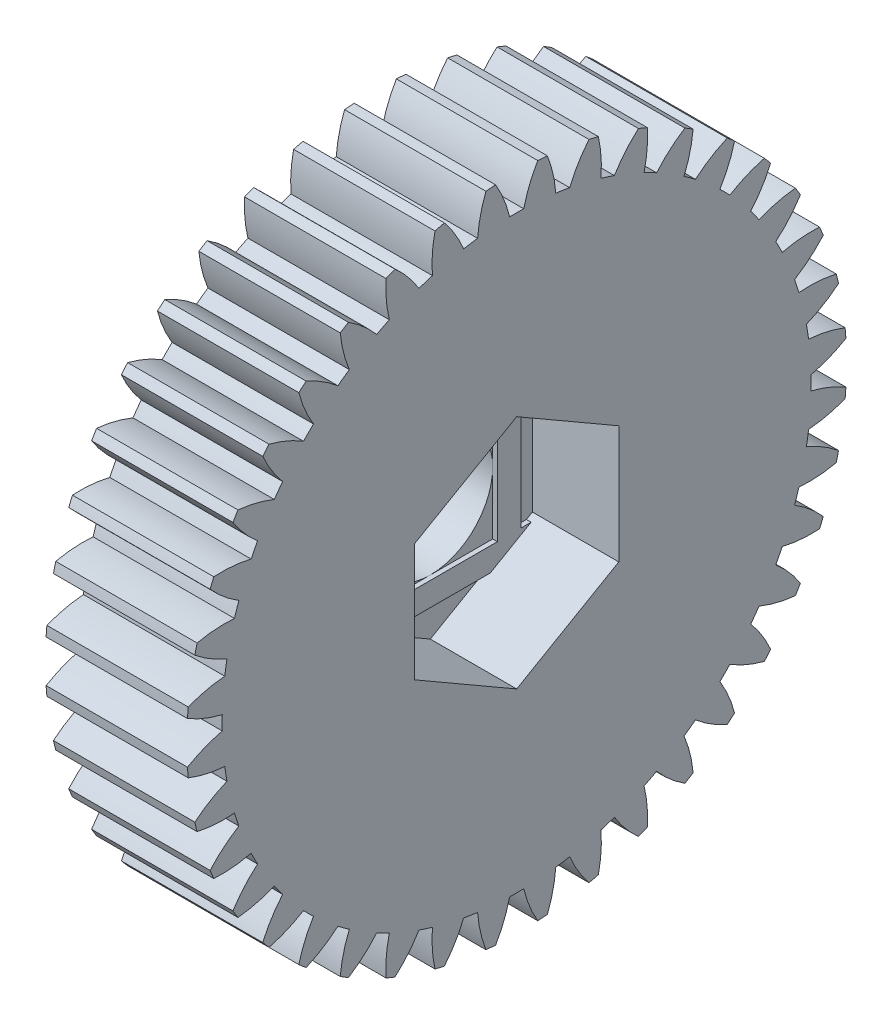
SolidWorks part; units mm, degrees
ref_plane "Plane1" through (0, 0, 0) normal (0, 0, 1) x (1, 0, 0)
ref_plane "Plane2" through (0, 0, 0) normal (0, 1, 0) x (1, 0, 0)
ref_plane "Plane3" through (0, 0, 0) normal (1, 0, 0) x (0, 0, -1)
sketch "HoldingSke" plane through (0, 0, 0) normal (0, 1, 0) x (1, 0, 0)
  line L0 (0, 0) -> (0.766, -0.6428)
  line L1 (-15, 0) -> (100, 0) construction
  line L2 (0, 0) -> (-2.1039, 2.3779)
  line L3 (0, 0) -> (-11.863, 4.5341)
  line L4 (0, 0) -> (6.6156, 5.5511)
  line L5 (0, 0) -> (-46.8476, -17.4728)
  line L6 (0, 0) -> (-7.4607, -5.0337)
  line L7 (-2.1039, 2.3779) -> (8.6586, 51.2059)
  line L8 (-76.2, 54.61) -> (-75.5, 54.61)
  line L9 (-71.009, 38.7566) -> (-53.1078, 45.2721)
  line L10 (-76.2, 71.12) -> (104.1128, 71.12)
  line L11 (0, 0) -> (-9, 0)
  line L12 (-76.2, 101.6) -> (-76.162, 101.6)
  line L13 (24.9733, 27.94) -> (52.9518, 28.4284)
  line L14 (24.9733, 27.94) -> (24.9743, 27.94)
  line L15 (24.9733, 27.94) -> (100.4006, 29.5858)
  line L16 (-63.627, -1) -> (-12.827, -1)
  circle A0 centre (0, 0) radius 2
  circle A1 centre (0, 0) radius 18.749
  circle A2 centre (0, 0) radius 37.5
  circle A3 centre (0, 0) radius 2
  dimension "MHD" = 37.498
  dimension "Hub_dia" = 75
  dimension "Bore" = 4
  dimension "MBD" = 4
  dimension "Num_teeth" = 40
  dimension "Pitch" = 1
  dimension "Overall_len" = 50
  dimension "Show_teeth" = 40
  dimension "Thickness" = 9
  dimension "OAL" = 50.0001
  dimension "T_dim" = 0.7
  dimension "Ap" = 20
  dimension "H" = 19.05
  dimension "Pitch_radius" = 180.3128
  dimension "Width" = 9
  dimension "Backlash" = 0.038
  dimension "Addendum_fac" = 1
  dimension "Dedendum_fac" = 1.25
  dimension "Clearance_fac" = 0.25
  dimension "Dedendum_add" = 0.001
  dimension "Module" = 1
sketch "BasProSke" plane through (0, 0, 0) normal (0, 1, 0) x (1, 0, 0)
  line L0 (-10, 0) -> (60, 0) construction
  line L1 (0, 0) -> (0, 21)
  line L2 (0, 0) -> (9, 0)
  line L3 (9, 0) -> (9, 21)
  line L4 (9, 21) -> (0, 21)
  dimension "Thickness" = 9
  dimension "Diameter" = 42
revolve "Base-Revolve" add sketch "BasProSke" angle 360 about L0
sketch "TooCutSke" plane through (0, 0, 0) normal (1, 0, 0) x (0, 0, -1)
  line L1 (0, 0) -> (0, 107) construction
  line L2 (0, 0) -> (-0.8517, 19.9819) construction
  line L3 (0, 0) -> (-3.1363, 39.8509) construction
  line L4 (-0.8517, 19.9819) -> (-1.5682, 19.9255) construction
  arc A0 (0.4487, 18.7436) -> (-0.4487, 18.7436) centre (0, 0) ccw
  arc A1 (1.3547, 20.9817) -> (-1.3547, 20.9817) centre (0, 0) ccw
  circle A2 centre (0, 0) radius 20 construction
  circle A3 centre (0, 0) radius 18.7939 construction
  arc A4 (-0.4487, 18.7436) -> (-1.3547, 20.9817) centre (-8.2322, 16.895) ccw
  arc A5 (1.3547, 20.9817) -> (0.4487, 18.7436) centre (8.2322, 16.895) ccw
  dimension "Root_dia" = 37.498
  dimension "Overcut_dia" = 42.0508
  dimension "Pitch_dia" = 40
  dimension "Base_dia" = 37.5877
  dimension "Flank_rad" = 8
  dimension "Half_ang" = 4.5
  dimension "Half_CT" = 0.7187
extrude "ToothCut" cut sketch "TooCutSke" along normal through all
fillet "Breaks" [suppressed] radius 0.02 tangent propagation no
fillet "RootFillets" [suppressed] radius 0.251
pattern_circular "TeethCuts" count 40 every 9 about axis through (-10, 0, 0) along (1, 0, 0) of "ToothCut", "RootFillets", "Breaks"
sketch "HubNeaOneSke" plane through (0, 0, 0) normal (-1, 0, 0) x (0, 0, 1)
  circle A0 centre (0, 0) radius 18.749
  dimension "Diameter" = 37.498
extrude "HubNearOne" [suppressed] add sketch "HubNeaOneSke" along normal blind 41.0001
sketch "HubNeaBotSke" plane through (0, 0, 0) normal (-1, 0, 0) x (0, 0, 1)
  circle A0 centre (0, 0) radius 18.749
  dimension "Diameter" = 37.498
extrude "HubNearBoth" [suppressed] add sketch "HubNeaBotSke" along normal blind 20.5
ref_plane "FarPln" through (9, 0, 0) normal (1, 0, 0) x (0, 0, -1)
sketch "HubFarSke" plane through (9, 0, 0) normal (1, 0, 0) x (0, 0, -1)
  circle A0 centre (0, 0) radius 18.749
  dimension "Diameter" = 37.498
extrude "HubFar" [suppressed] add sketch "HubFarSke" along normal blind 20.5
sketch "BorSke" plane through (0, 0, 0) normal (1, 0, 0) x (0, 0, -1)
  circle A0 centre (0, 0) radius 2
  dimension "Diameter" = 4
extrude "Bore" cut sketch "BorSke" along normal mid plane 100.0001
sketch "KeySke" plane through (0, 0, 0) normal (1, 0, 0) x (0, 0, -1)
  line L0 (-0.8, 0) -> (-0.8, 2.7)
  line L1 (-0.8, 2.7) -> (0.8, 2.7)
  line L2 (0.8, 2.7) -> (0.8, 0)
  line L3 (0, 0) -> (0, 34) construction
  line L4 (-0.8, 0) -> (0.8, 0)
  dimension "Offset" = 2.7
  dimension "Width" = 1.6
extrude "Keyway" [suppressed] cut sketch "KeySke" along normal mid plane 100.0001
pattern_circular "Keyway2" [suppressed] count 2 every 90 about axis through (-10, 0, 0) along (1, 0, 0) reverse direction yes
sketch "Sketch1" plane through (9, 0, 0) normal (1, 0, 0) x (0, 0, -1)
  line L1 (0, 7.5056) -> (-6.5, 3.7528)
  line L2 (-6.5, 3.7528) -> (-6.5, -3.7528)
  line L3 (-6.5, -3.7528) -> (0, -7.5056)
  line L4 (0, -7.5056) -> (6.5, -3.7528)
  line L5 (6.5, -3.7528) -> (6.5, 3.7528)
  line L6 (6.5, 3.7528) -> (0, 7.5056)
  circle A0 centre (0, 0) radius 7.5056
  circle A2 centre (0, 0) radius 6.5 construction
  circle A3 centre (0, 0) radius 3.9725
  dimension "D1" = 7.945
  dimension "D2" = 13
extrude "Cut-Extrude1" cut sketch "Sketch1" against normal blind 5.5 contours L1 L2 L3 L4 L5 L6
extrude "Cut-Extrude2" cut sketch "Sketch1<7>" against normal through all contours A3 region at (9, 0, 0)
sketch "Sketch1<7>" plane through (9, 0, 0) normal (1, 0, 0) x (0, 0, -1) same geometry as "Sketch1"
sketch "Sketch2" plane through (0, 0, 0) normal (-1, 0, 0) x (0, 0, 1)
  circle A0 centre (0, 0) radius 6
  circle A1 centre (0, 0) radius 4
  dimension "D1" = 12
  dimension "D2" = 8
extrude "Boss-Extrude1" add sketch "Sketch2" along normal blind 1.3
sketch "Sketch3" plane through (3.5, 0, 0) normal (1, 0, 0) x (0, 0, -1)
  line L1 (3.9725, 3.9725) -> (-3.9725, 3.9725)
  line L2 (3.9725, 3.9725) -> (3.9725, -3.9725)
  line L3 (3.9725, -3.9725) -> (-3.9725, -3.9725)
  line L4 (-3.9725, 3.9725) -> (-3.9725, -3.9725)
  line L6 (5.4725, 5.4725) -> (5.4725, -5.4725)
  line L7 (5.4725, -5.4725) -> (-5.4725, -5.4725)
  line L8 (-5.4725, 5.4725) -> (-5.4725, -5.4725)
  line L9 (5.4725, 5.4725) -> (-5.4725, 5.4725)
  line L10 (5.4725, 3.9725) -> (6.1194, 3.9725)
  line L11 (6.5, 3.7528) -> (0, 7.5056) construction
  line L12 (5.4725, -3.9725) -> (6.1194, -3.9725)
  line L13 (0, -7.5056) -> (6.5, -3.7528) construction
  line L14 (-5.4725, -3.9725) -> (-6.1194, -3.9725)
  line L15 (-6.5, -3.7528) -> (0, -7.5056) construction
  line L16 (-5.4725, 3.9725) -> (-6.1194, 3.9725)
  line L17 (0, 7.5056) -> (-6.5, 3.7528) construction
  circle A0 centre (0, 0) radius 3.9725 construction
  point P26 (0, 0)
  line M10 (6.5, 3.7528) -> (0, 7.5056)
  line M11 (0, 7.5056) -> (-6.5, 3.7528)
  line M13 (-6.5, -3.7528) -> (0, -7.5056)
  line M14 (0, -7.5056) -> (6.5, -3.7528)
  dimension "D1" = 1.5
extrude "Boss-Extrude2" add sketch "Sketch3" along normal blind 0.3 contours L9 L8 L7 L6 L4 L1 L2 L3 M10 M11 M13 M14 | L12 L6 M14 | L6 L10 M10 | L16 L8 M11 | L8 L14 M13 region at (3.5, 0, -5.3177) region at (3.5, 4.097, -5.6881) region at (3.5, -4.097, -5.6881) region at (3.5, 4.097, 5.6881) region at (3.5, -4.097, 5.6881)
equation "' \"Module@HoldingSke\" = 6.35"
equation "' \"Num_teeth@HoldingSke\" = 12"
equation "' \"Ap@HoldingSke\" =  20"
equation "' \"Ap@HoldingSke\" = 20"
equation "' \"Width@HoldingSke\" = 0.5 * 25.4"
equation "' \"Hub_dia@HoldingSke\"= 1 * 25.4"
equation "' \"Hub_dia@HoldingSke\" = 1 * 25.4"
equation "' \"Overall_len@HoldingSke\" = 1.0 * 25.4"
equation "' \"Bore@HoldingSke\" = 0.75 * 25.4"
equation "' \"T_dim@HoldingSke\" = 0.1 * 25.4"
equation "' \"Width@KeySke\" = 0.25 * 25.4"
equation "' \"Show_teeth@HoldingSke\" = 13"
equation "' \"Backlash@HoldingSke\" = 0.009 * 25.4"
equation "' \"Addendum_fac@HoldingSke\" = 1.0"
equation "' \"Dedendum_fac@HoldingSke\" = 1.25"
equation "' \"Dedendum_add@HoldingSke\" = 0.00005 * 25.4"
equation "' \"Clearance_fac@HoldingSke\" = 0.25"
equation "\"Pitch@HoldingSke\" = 1 / \"Module@HoldingSke\""
equation "\"Overcut_dia@TooCutSke\" = (\"Num_teeth@HoldingSke\" + 2 * \"Addendum_fac@HoldingSke\") / \"Pitch@HoldingSke\" + 0.002 * 25.4"
equation "\"Pitch_dia@TooCutSke\" = \"Num_teeth@HoldingSke\" / \"Pitch@HoldingSke\""
equation "\"Base_dia@TooCutSke\" = \"Num_teeth@HoldingSke\" / \"Pitch@HoldingSke\" * cos((\"Ap@HoldingSke\"  * 3.14159265 / 180))"
equation "\"Root_dia@TooCutSke\" = (\"Num_teeth@HoldingSke\" + 2) / \"Pitch@HoldingSke\" - 2 * (\"Addendum_fac@HoldingSke\" + \"Dedendum_fac@HoldingSke\") / \"Pitch@HoldingSke\" - \"Dedendum_add@HoldingSke\" * 2"
equation "\"Half_ang@TooCutSke\" = 180 / \"Num_teeth@HoldingSke\""
equation "\"Half_CT@TooCutSke\" = \"Num_teeth@HoldingSke\" / \"Pitch@HoldingSke\" * sin((3.14159265 / 2 / \"Num_teeth@HoldingSke\")) / 2 - 7 * \"Backlash@HoldingSke\" / 4"
equation "\"Flank_rad@TooCutSke\" = \"Num_teeth@HoldingSke\" / \"Pitch@HoldingSke\" / 5"
equation "\"Radius@RootFillets\" = \"Clearance_fac@HoldingSke\" / \"Pitch@HoldingSke\" + \"Dedendum_add@HoldingSke\""
equation "\"Break_rad@Breaks\" = 0.02 / \"Pitch@HoldingSke\""
equation "\"Thickness@HoldingSke\" = \"Width@HoldingSke\""
equation "\"OAL@HoldingSke\" = \"Thickness@HoldingSke\""
equation "\"MHD@HoldingSke\" = (\"Num_teeth@HoldingSke\" + 2) / \"Pitch@HoldingSke\" - 2 * (\"Addendum_fac@HoldingSke\" + \"Dedendum_fac@HoldingSke\")  / \"Pitch@HoldingSke\" - \"Dedendum_add@HoldingSke\" * 2"
equation "\"MBD@HoldingSke\" = (\"Num_teeth@HoldingSke\" + 2) / \"Pitch@HoldingSke\" - 2 * (\"Addendum_fac@HoldingSke\" + \"Dedendum_fac@HoldingSke\")  / \"Pitch@HoldingSke\" - \"Dedendum_add@HoldingSke\" * 2 - 0.002 * 25.4"
equation "\"MHD@HoldingSke\" = ((sgn( \"MHD@HoldingSke\" - \"Hub_dia@HoldingSke\" )-1)*( \"MHD@HoldingSke\" - \"Hub_dia@HoldingSke\" ))/-2+ \"Hub_dia@HoldingSke\""
equation "\"MBD@HoldingSke\" = ((sgn( \"MBD@HoldingSke\" - \"Bore@HoldingSke\" )-1)*( \"MBD@HoldingSke\" - \"Bore@HoldingSke\" ))/-2+ \"Bore@HoldingSke\""
equation "\"OAL@HoldingSke\" = ((sgn( \"OAL@HoldingSke\" - \"Overall_len@HoldingSke\" )+1)*( \"OAL@HoldingSke\" - \"Overall_len@HoldingSke\" ))/2 + \"Overall_len@HoldingSke\" + 0.000002 * 25.4"
equation "\"Num_teeth@TeethCuts\" = int( \"Show_teeth@HoldingSke\" ) + 1"
equation "\"Num_teeth@TeethCuts\" = ((sgn( \"Num_teeth@TeethCuts\" - \"Num_teeth@HoldingSke\" )-1)*( \"Num_teeth@TeethCuts\" - \"Num_teeth@HoldingSke\" ))/-2+ \"Num_teeth@HoldingSke\""
equation "\"Num_teeth@TeethCuts\" = ((sgn( \"Num_teeth@TeethCuts\" - 2.0)+1)*( \"Num_teeth@TeethCuts\" - 2.0))/2 +2.0"
equation "\"Angle@TeethCuts\" = 360.0 / \"Num_teeth@HoldingSke\""
equation "\"Diameter@BasProSke\" = (\"Num_teeth@HoldingSke\" + 2 * \"Addendum_fac@HoldingSke\") / \"Pitch@HoldingSke\""
equation "\"Thickness@BasProSke\"  = \"Thickness@HoldingSke\""
equation "' \"Fillet_rad@BasProSke\" =  \"Thickness@HoldingSke\" * 0.05"
equation "' \"Fillet_rad@BasProSke\" = \"Thickness@HoldingSke\" * 0.05"
equation "\"MHD@HoldingSke\" = ((sgn( \"MHD@HoldingSke\" - \"Root_dia@TooCutSke\" )-1)*( \"MHD@HoldingSke\" - \"Root_dia@TooCutSke\" ))/-2+ \"Root_dia@TooCutSke\""
equation "\"Diameter@HubNeaOneSke\" = \"MHD@HoldingSke\""
equation "\"Length@HubNearOne\" = \"OAL@HoldingSke\" - \"Thickness@BasProSke\""
equation "\"Diameter@HubNeaBotSke\" = \"MHD@HoldingSke\""
equation "\"Length@HubNearBoth\" = ( \"OAL@HoldingSke\" - \"Thickness@BasProSke\" ) / 2.0"
equation "\"Thickness@FarPln\" = \"Thickness@BasProSke\""
equation "\"Diameter@HubFarSke\" = \"MHD@HoldingSke\""
equation "\"Length@HubFar\" = ( \"OAL@HoldingSke\" - \"Thickness@BasProSke\" ) / 2.0"
equation "\"Diameter@BorSke\" = \"MBD@HoldingSke\""
equation "\"D1@Bore\" = \"OAL@HoldingSke\" * 2.0"
equation "\"D1@Keyway\" = \"OAL@HoldingSke\" * 2.0"
equation "\"Offset@KeySke\" = \"T_dim@HoldingSke\" + \"MBD@HoldingSke\" / 2.0"
